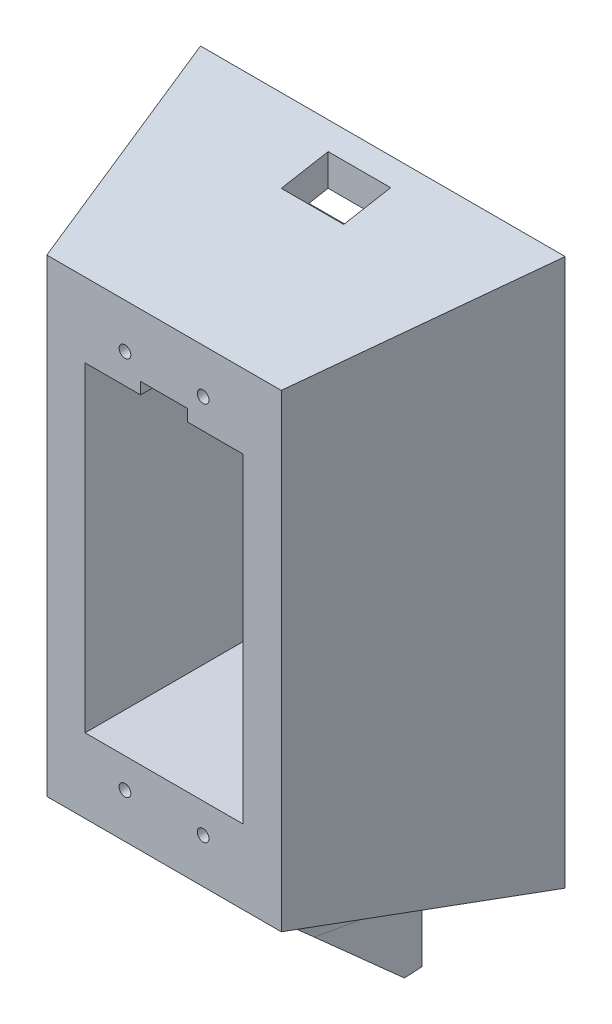
SolidWorks part; units mm, degrees
ref_plane "Plano frontal" through (0, 0, 0) normal (0, 0, 1) x (1, 0, 0)
ref_plane "Plano superior" through (0, 0, 0) normal (0, 1, 0) x (1, 0, 0)
ref_plane "Plano direito" through (0, 0, 0) normal (1, 0, 0) x (0, 0, -1)
sketch "Esboço1" plane through (0, 0, 0) normal (0, 0, 1) x (1, 0, 0)
  line L1 (-15, -30) -> (15, -30)
  line L2 (-15, -30) -> (-15, 30)
  line L3 (-15, 30) -> (15, 30)
  line L4 (15, -30) -> (15, 30)
  line L5 (-15, -30) -> (15, 30) construction
  line L6 (-15, 30) -> (15, -30) construction
  point P0 (0, 0)
  dimension "D1" = 60
ref_plane "Plano1" through (0, 0, -28) normal (0, 0, 1) x (1, 0, 0)
sketch "Esboço2" plane through (0, 0, -28) normal (0, 0, 1) x (1, 0, 0)
  line L1 (-23.3333, -35) -> (23.3333, -35)
  line L2 (-23.3333, -35) -> (-23.3333, 35)
  line L3 (-23.3333, 35) -> (23.3333, 35)
  line L4 (23.3333, -35) -> (23.3333, 35)
  line L5 (-23.3333, -35) -> (23.3333, 35) construction
  line L6 (-23.3333, 35) -> (23.3333, -35) construction
  dimension "D1" = 70
loft "Loft1" add profiles "Esboço1", "Esboço2" connector at (-15, -30, 0) connector at (-23.3333, -35, -28)
sketch "Esboço3" plane through (0, 0, 0) normal (0, 0, 1) x (1, 0, 0)
  line L1 (-10.1, -20.5) -> (10.1, -20.5)
  line L2 (-10.1, -20.5) -> (-10.1, 20.5)
  line L3 (-10.1, 20.5) -> (10.1, 20.5)
  line L4 (10.1, -20.5) -> (10.1, 20.5)
  line L5 (-10.1, -20.5) -> (10.1, 20.5) construction
  line L6 (-10.1, 20.5) -> (10.1, -20.5) construction
  point P0 (0, 0)
  dimension "D1" = 41
  dimension "D2" = 20.2
extrude "Corte-extrusão1" cut sketch "Esboço3" against normal through all
shell "Casca1" thickness 4 removed face at (0, 0, -28)
sketch "Esboço5" plane through (0, 0, -28) normal (0, 0, 1) x (1, 0, 0)
  line L0 (0, 0) -> (0, 6.0662) construction
  line L1 (0, 0) -> (5.9294, 0) construction
  line L31 (10.1, 20.5) -> (10.1, 30.9367)
  line L32 (19.1599, 30.9367) -> (-19.1599, 30.9367) construction
  line L33 (10.1, 30.9367) -> (19.1599, 30.9367)
  line L34 (19.1599, 30.9367) -> (19.1599, 20.5)
  line L35 (19.1599, -30.9367) -> (19.1599, 30.9367) construction
  line L36 (19.1599, 20.5) -> (10.1, 20.5)
  line L37 (19.1599, -20.5) -> (10.1, -20.5)
  line L38 (19.1599, -30.9367) -> (19.1599, -20.5)
  line L39 (10.1, -30.9367) -> (19.1599, -30.9367)
  line L40 (10.1, -20.5) -> (10.1, -30.9367)
  line L41 (-10.1, -20.5) -> (-10.1, -30.9367)
  line L42 (-10.1, -30.9367) -> (-19.1599, -30.9367)
  line L43 (-19.1599, -30.9367) -> (-19.1599, -20.5)
  line L44 (-19.1599, -20.5) -> (-10.1, -20.5)
  line L45 (-19.1599, 20.5) -> (-10.1, 20.5)
  line L46 (-19.1599, 30.9367) -> (-19.1599, 20.5)
  line L47 (-10.1, 30.9367) -> (-19.1599, 30.9367)
  line L48 (-10.1, 20.5) -> (-10.1, 30.9367)
extrude "Ressalto-extrusão3" add sketch "Esboço5" along normal up to next
sketch "Esboço6" plane through (0, 0, -28) normal (0, 0, -1) x (-1, 0, 0)
  line L2 (0, 0) -> (0, 4.4519) construction
  line L3 (0, 0) -> (-5.2651, 0) construction
  circle A0 centre (-15, 25) radius 0.5
  circle A1 centre (15, 25) radius 0.5
  circle A2 centre (15, -25) radius 0.5
  circle A3 centre (-15, -25) radius 0.5
  dimension "D1" = 1
  dimension "D2" = 30
  dimension "D3" = 50
extrude "Corte-extrusão2" cut sketch "Esboço6" against normal blind 5
sketch "Esboço7" plane through (0, 0, 0) normal (0, 0, 1) x (1, 0, 0)
  line L0 (10.1, 20.5) -> (-10.1, 20.5) construction
  line L1 (-5, 24.3) -> (5, 24.3) construction
  line L2 (0, 0) -> (-2.5167, 0) construction
  line L3 (-10.1, -20.5) -> (10.1, -20.5) construction
  circle A0 centre (-5, 24.3) radius 0.75
  circle A1 centre (5, 24.3) radius 0.75
  circle A2 centre (-5, -24.3) radius 0.75
  circle A3 centre (5, -24.3) radius 0.75
  point P6 (0, 24.3)
  point P7 (0, 20.5)
  dimension "D1" = 10
  dimension "D3" = 1.5
  dimension "D4" = 1.5
  dimension "D2" = 3.8
  dimension "D5" = 3.8
extrude "Corte-extrusão3" cut sketch "Esboço7" against normal blind 3
sketch "Esboço8" plane through (0, 0, 0) normal (1, 0, 0) x (0, 0, -1)
  line L0 (28, -35) -> (28, -55)
  line L2 (0, -30) -> (28, -35)
  line L7 (0, -30) -> (28, -55)
  dimension "D1" = 20
extrude "Ressalto-extrusão4" add sketch "Esboço8" along normal mid plane 10
fillet "Filete2" radius 10 2 edges
chamfer "Chanfro3" distance 3 angle 45 1 edges at (0, -55, -28) first distance on face at (-0.625, -37.8867, -8.833)
sketch "Esboço9" plane through (0, 0, -28) normal (0, 0, -1) x (-1, 0, 0)
  line L0 (5, -53.002) -> (-5, -53.002) construction
  circle A0 centre (0, -45.002) radius 0.5
  dimension "D1" = 8
  dimension "D3" = 1
  dimension "D2" = 5
extrude "Corte-extrusão4" cut sketch "Esboço9" against normal blind 3
sketch "Esboço11" plane through (0, -20.5, 0.8002) normal (0, 1, 0) x (1, 0, 0)
  line L6 (-4, 25.8002) -> (4, 25.8002)
  line L8 (-4, 25.8002) -> (-4, 19.8002)
  line L9 (-4, 19.8002) -> (4, 19.8002)
  line L10 (4, 25.8002) -> (4, 19.8002)
  line L11 (-4, 25.8002) -> (4, 19.8002) construction
  line L12 (-4, 19.8002) -> (4, 25.8002) construction
  point P0 (0, 22.8002)
  dimension "D1" = 8
  dimension "D2" = 3
  dimension "D4" = 6
extrude "Corte-extrusão7" cut sketch "Esboço11" along normal through all
sketch "Esboço12" plane through (0, 0, 0) normal (0, 0, 1) x (1, 0, 0)
  line L0 (10.1, 20.5) -> (-10.1, 20.5) construction
  line L1 (-3, 19) -> (3, 19)
  line L2 (-3, 19) -> (-3, 22)
  line L3 (-3, 22) -> (3, 22)
  line L4 (3, 19) -> (3, 22)
  line L5 (-3, 19) -> (3, 22) construction
  line L6 (-3, 22) -> (3, 19) construction
  point P0 (0, 20.5)
  dimension "D1" = 6
  dimension "D2" = 3
extrude "Corte-extrusão6" cut sketch "Esboço12" against normal blind 22
